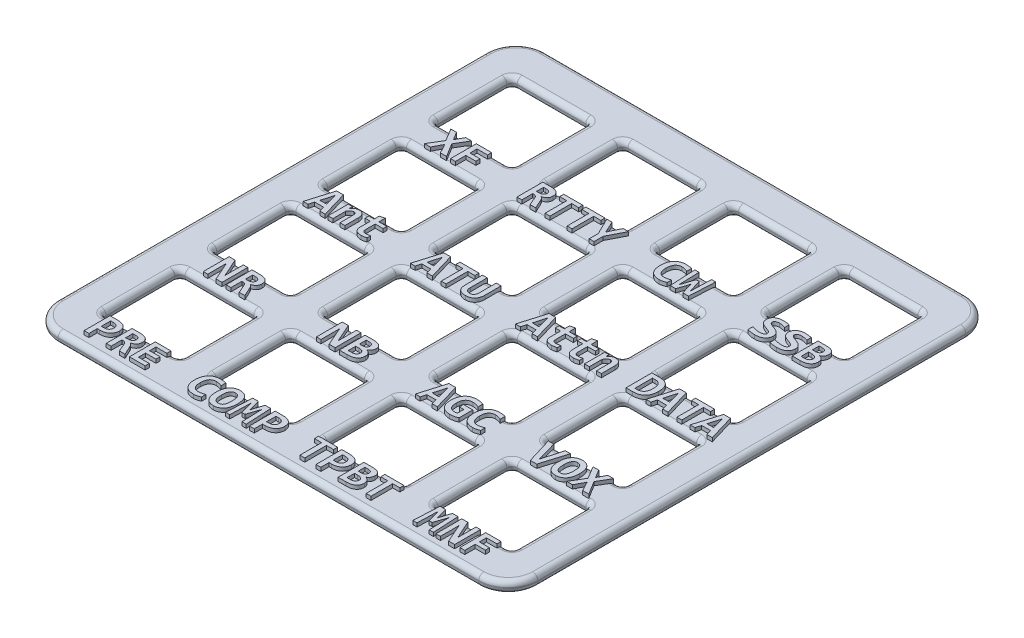
SolidWorks part; units mm, degrees
ref_plane "Front" through (0, 0, 0) normal (0, 0, 1) x (1, 0, 0)
ref_plane "Top" through (0, 0, 0) normal (0, 1, 0) x (1, 0, 0)
ref_plane "Right" through (0, 0, 0) normal (1, 0, 0) x (0, 0, -1)
sketch "Sketch1" plane through (0, 0, 0) normal (0, 1, 0) x (1, 0, 0)
  line L1 (-14.8807, -14.5355) -> (42.1193, -14.5355)
  line L2 (-18.8807, -18.5355) -> (-18.8807, -76.5355)
  line L3 (-14.8807, -80.5355) -> (42.1193, -80.5355)
  line L4 (46.1193, -18.5355) -> (46.1193, -76.5355)
  arc A0 (-14.8807, -14.5355) -> (-18.8807, -18.5355) centre (-14.8807, -18.5355) ccw
  arc A1 (46.1193, -18.5355) -> (42.1193, -14.5355) centre (42.1193, -18.5355) ccw
  arc A2 (42.1193, -80.5355) -> (46.1193, -76.5355) centre (42.1193, -76.5355) ccw
  arc A3 (-18.8807, -76.5355) -> (-14.8807, -80.5355) centre (-14.8807, -76.5355) ccw
  dimension "D1" = 65
  dimension "D2" = 66
extrude "main" add sketch "Sketch1" along normal blind 1.5
sketch "Sketch2" plane through (0, 1.5, 0) normal (0, 1, 0) x (1, 0, 0)
  line L0 (42.1193, -14.5355) -> (-14.8807, -14.5355) construction
  line L1 (-14.2307, -19.6855) -> (-3.5307, -19.6855)
  line L2 (-14.2307, -19.6855) -> (-14.2307, -30.3855)
  line L3 (-14.2307, -30.3855) -> (-3.5307, -30.3855)
  line L4 (-3.5307, -19.6855) -> (-3.5307, -30.3855)
  line L5 (-18.8807, -18.5355) -> (-18.8807, -76.5355) construction
  point P4 (-8.8807, -19.6855)
  dimension "D1" = 5.15
  dimension "D2" = 4.65
  dimension "D3" = 10.7
  dimension "D4" = 10.7
extrude "button hole 1" cut sketch "Sketch2" against normal through all
fillet "button fillet" radius 0.7 12 edges at (-8.8807, 0, 30.3855) (-8.8807, 1.5, 30.3855) (-8.8807, 0, 19.6855) (-8.8807, 1.5, 19.6855) (-3.5307, 0.75, 30.3855) (-3.5307, 0, 25.0355) (-3.5307, 0.75, 19.6855) (-3.5307, 1.5, 25.0355) (-14.2307, 0.75, 19.6855) (-14.2307, 0, 25.0355) (-14.2307, 0.75, 30.3855) (-14.2307, 1.5, 25.0355)
pattern_linear "buttons by 16" count 4 spacing 15 along (1, 0, 0) count 4 spacing 15 along (0, 0, 1) of "button fillet", "button hole 1"
fillet "outer edge fillet" radius 0.7 16 edges at (13.6193, 1.5, 14.5355) (13.6193, 0, 14.5355) (46.1193, 1.5, 47.5355) (46.1193, 0, 47.5355) (13.6193, 1.5, 80.5355) (13.6193, 0, 80.5355) (-18.8807, 1.5, 47.5355) (-18.8807, 0, 47.5355) (44.9477, 1.5, 15.7071) (44.9477, 1.5, 79.364) (-17.7092, 1.5, 79.364) (-17.7092, 1.5, 15.7071) (44.9477, 0, 15.7071) (44.9477, 0, 79.364) (-17.7092, 0, 79.364) (-17.7092, 0, 15.7071)
sketch "Lettering" plane through (0, 0, 0) normal (0, 1, 0) x (1, 0, 0)
  line L0 (45.4193, -49.1355) -> (-18.1807, -49.1355) construction
  line L1 (45.4783, -79.1355) -> (-16.5217, -79.1355) construction
  line L2 (45.4193, -76.5355) -> (45.4193, -18.5355) construction
  line L3 (-18.1807, -18.5355) -> (-18.1807, -76.5355) construction
  line L5 (45.4193, -64.1355) -> (-18.1807, -64.1355) construction
  line L6 (45.4193, -76.5355) -> (45.4193, -18.5355) construction
  line L7 (-18.1807, -18.5355) -> (-18.1807, -76.5355) construction
  line L8 (45.4193, -34.1355) -> (-18.1807, -34.1355) construction
  line L11 (-14.8807, -80.5355) -> (42.1193, -80.5355) construction
  text T0 "SSB" font "Consolas" height 3.5
  text T1 "CW" font "Consolas" height 3.5
  text T2 "RTTY" font "Consolas" height 3.5
  text T3 "XF" font "Consolas" height 3.5
  text T4 "VOX" font "Consolas" height 3.5
  text T5 "AGC" font "Consolas" height 3.5
  text T6 "MNF" font "Consolas" height 3.5
  text T7 "Attn" font "Consolas" height 3.5
  text T8 "Ant" font "Consolas" height 3.5
  text T9 "TPBT" font "Consolas" height 3.5
  text T10 "COMP" font "Consolas" height 3.5
  text T11 "PRE" font "Consolas" height 3.5
  text T12 "DATA" font "Consolas" height 3.5
  text T13 "NB" font "Consolas" height 3.5
  text T14 "ATU" font "Consolas" height 3.5
  text T15 "NR" font "Consolas" height 3.5
  dimension "D1" = 46.4
  dimension "D2" = 16.4
  dimension "D3" = 1.4
  dimension "D4" = 31.4
extrude "lettering boss" add sketch "Lettering" along normal offset from surface (2 mm away) 0.5 up to face at (13.6193, 1.5, 47.5355) offset beyond the face yes
